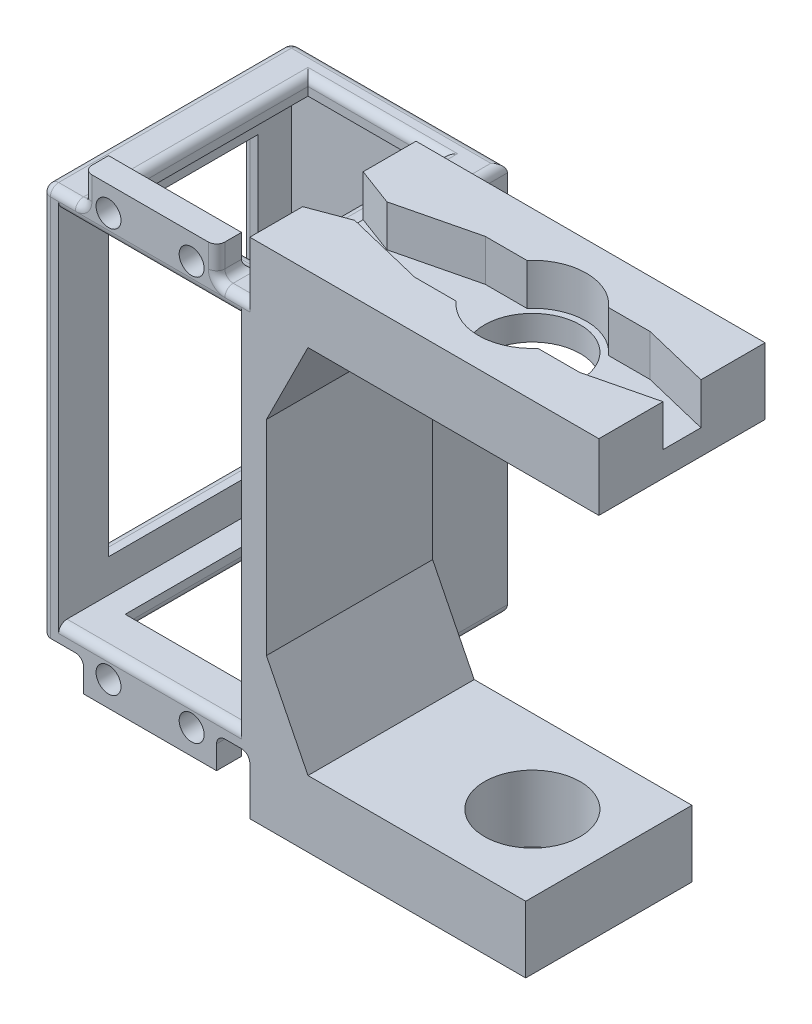
SolidWorks part; units mm, degrees
ref_plane "Front Plane" through (0, 0, 0) normal (0, 0, 1) x (1, 0, 0)
ref_plane "Top Plane" through (0, 0, 0) normal (0, 1, 0) x (1, 0, 0)
ref_plane "Right Plane" through (0, 0, 0) normal (1, 0, 0) x (0, 0, -1)
sketch "Sketch1" plane through (0, 0, 0) normal (0, 0, 1) x (1, 0, 0)
  line L1 (-13, 23.5) -> (13, 23.5)
  line L2 (-13, 23.5) -> (-13, -23.5)
  line L3 (-13, -23.5) -> (13, -23.5)
  line L4 (13, 23.5) -> (13, -23.5)
  line L5 (-13, 23.5) -> (13, -23.5) construction
  line L6 (-13, -23.5) -> (13, 23.5) construction
  point P0 (0, 0)
  dimension "D1" = 47
  dimension "D2" = 26
extrude "Boss-Extrude1" add sketch "Sketch1" along normal blind 30 contours L2 L1 L4 L3
shell "Shell1" thickness 2
sketch "Sketch2" plane through (0, 0, 30) normal (0, 0, 1) x (1, 0, 0)
  line L1 (-5, 24.3) -> (5, 24.3)
  line L2 (-5, 24.3) -> (-5, -24.3)
  line L3 (-5, -24.3) -> (5, -24.3)
  line L4 (5, 24.3) -> (5, -24.3)
  line L5 (-5, 24.3) -> (5, -24.3) construction
  line L6 (-5, -24.3) -> (5, 24.3) construction
  line L10 (-8, 27.3) -> (-8, -27.3)
  line L11 (-13, 23.5) -> (13, 23.5)
  line L12 (-13, 23.5) -> (-13, -23.5)
  line L13 (-13, -23.5) -> (13, -23.5)
  line L14 (13, 23.5) -> (13, -23.5)
  line L15 (-8, -27.3) -> (8, -27.3)
  line L16 (8, 27.3) -> (8, -27.3)
  line L17 (-8, 27.3) -> (8, 27.3)
  point P0 (0, 0)
  line M3 (-13, -23.5) -> (13, -23.5)
  line M5 (13, 23.5) -> (-13, 23.5)
  dimension "D1" = 10
  dimension "D2" = 48.6
  dimension "D3" = 3
extrude "Boss-Extrude2" add sketch "Sketch2" against normal blind 3 contours L17 L10 L2 L1 L4 L11 L16 M5 | L4 L1 L2 M5 | L16 L4 L3 L2 L10 L15 M3 | L4 L2 L3 M3
sketch "Sketch3" plane through (0, 0, 30) normal (0, 0, 1) x (1, 0, 0)
  line L1 (-5, 24.3) -> (5, 24.3) construction
  line L2 (-5, 24.3) -> (-5, -24.3) construction
  line L3 (-5, -24.3) -> (5, -24.3) construction
  line L4 (5, 24.3) -> (5, -24.3) construction
  line L5 (-5, 24.3) -> (5, -24.3) construction
  line L6 (-5, -24.3) -> (5, 24.3) construction
  circle A0 centre (-5, -24.3) radius 1.5
  circle A1 centre (5, -24.3) radius 1.5
  circle A2 centre (5, 24.3) radius 1.5
  circle A3 centre (-5, 24.3) radius 1.5
  point P0 (0, 0)
  dimension "D3" = 3
  dimension "D1" = 48.6
  dimension "D2" = 10
extrude "Cut-Extrude1" cut sketch "Sketch3" against normal blind 3
sketch "Sketch4" plane through (0, 0, 30) normal (0, 0, 1) x (1, 0, 0)
  line L0 (14, 0) -> (24, 0) construction
  line L1 (-24, 22.3) -> (24, 22.3)
  line L2 (-24, 22.3) -> (-24, -22.3)
  line L3 (-24, -22.3) -> (24, -22.3)
  line L4 (24, 22.3) -> (24, -22.3)
  line L5 (-24, 22.3) -> (24, -22.3) construction
  line L6 (-24, -22.3) -> (24, 22.3) construction
  line L7 (24, -22.3) -> (14, -22.3)
  line L8 (24, -22.3) -> (24, 22.3)
  line L9 (24, 22.3) -> (14, 22.3)
  line L10 (14, -22.3) -> (14, 22.3)
  line L11 (0, 0) -> (13, 0)
  line L12 (0, 0) -> (0, 23.5)
  line L13 (0, 23.5) -> (13, 23.5)
  line L14 (13, 0) -> (13, 23.5)
  line L15 (12, 22.3) -> (54, 22.3)
  line L16 (12, 22.3) -> (12, 30.3)
  line L17 (12, 30.3) -> (54, 30.3)
  line L18 (54, 22.3) -> (54, 30.3)
  line L19 (14, 12.3) -> (19, 22.3)
  line L20 (14, -12.3) -> (19, -22.3)
  line L21 (12, -30.3) -> (54, -30.3)
  line L22 (54, -22.3) -> (54, -30.3)
  line L23 (12, -22.3) -> (54, -22.3)
  line L24 (12, -22.3) -> (12, -30.3)
  point P0 (0, 0)
  point P8 (19, 22.3)
  point P20 (14, 12.3)
  line M10 (13, -23.5) -> (13, 23.5)
  dimension "D1" = 48
  dimension "D2" = 44.6
  dimension "D3" = 10
  dimension "D4" = 5
  dimension "D5" = 8
  dimension "D6" = 42
  dimension "D7" = 10
extrude "Boss-Extrude3" add sketch "Sketch4" against normal blind 20 contours L15 L18 L17 L16 L1 M10 | L10 L19 L1 | L3 L10 L1 M10 | L20 L10 L3 | L24 L21 L22 L23 L7 L3 M10
sketch "Sketch5" plane through (0, 22.3, 0) normal (0, -1, 0) x (-1, 0, 0)
  line L0 (-36, -30) -> (-36, -10)
  line L1 (-19, -10) -> (-54, -10)
  line L2 (-19, -10) -> (-19, -30)
  line L3 (-19, -30) -> (-54, -30)
  line L4 (-54, -10) -> (-54, -30)
  circle A0 centre (-36, -20) radius 5.75
  dimension "D2" = 11.5
  dimension "D1" = 17
extrude "Cut-Extrude2" cut sketch "Sketch5" against normal through all both and the other way through all contours L0 A0 | L0 A0
sketch "Sketch6" plane through (0, 0, 0) normal (0, 0, -1) x (-1, 0, 0)
  line L1 (-13, 23.5) -> (13, 23.5)
  line L2 (-13, 23.5) -> (-13, -23.5)
  line L3 (-13, -23.5) -> (13, -23.5)
  line L4 (13, 23.5) -> (13, -23.5)
  circle A0 centre (0, 0) radius 4.5
  circle A1 centre (0, -10) radius 4.5
  dimension "D1" = 9
  dimension "D2" = 2
extrude "Boss-Extrude4" add sketch "Sketch6" along normal blind 8 contours A1
sketch "Sketch7" plane through (0, 23.5, 0) normal (0, 1, 0) x (1, 0, 0)
  line L0 (8, -25) -> (8, -5)
  line L1 (13, -30) -> (-13, -30)
  line L2 (13, -30) -> (13, 0)
  line L3 (13, 0) -> (-13, 0)
  line L4 (-13, -30) -> (-13, 0)
  line L5 (8, -5) -> (-8, -5) construction
  line L6 (-8, -25) -> (-8, -5)
  line L7 (8, -25) -> (-8, -25)
  line L8 (8, -23) -> (8, -3)
  line L9 (8, -3) -> (-8, -3)
  line L10 (-8, -23) -> (-8, -3)
  line L11 (8, -23) -> (-8, -23) construction
  point P10 (13, 0)
  dimension "3" = 3
  dimension "D1" = 5
  dimension "D2" = 2
extrude "Cut-Extrude3" cut sketch "Sketch7" against normal through all both and the other way through all contours L10 L6 L7 L0 L8 L9
sketch "Sketch9" plane through (0, 30.3, 0) normal (0, 1, 0) x (1, 0, 0)
  line L0 (31.0819, -24.25) -> (31.0819, -15.75)
  line L1 (-30, 10) -> (54, 10)
  line L2 (-30, 10) -> (-30, -30)
  line L3 (-30, -30) -> (54, -30)
  line L4 (54, 10) -> (54, -30)
  line L5 (-30, 10) -> (54, -30) construction
  line L6 (-30, -30) -> (54, 10) construction
  line L7 (36, -20) -> (29.5, -20) construction
  line L8 (31.0819, -15.75) -> (26.0819, -15.75)
  line L9 (31.0819, -24.25) -> (26.0819, -24.25)
  line L10 (26.0819, -15.75) -> (16.5595, -18.066)
  line L11 (26.0819, -24.25) -> (16.5595, -21.934)
  line L12 (16.5595, -18.066) -> (10.3634, -15.75)
  line L13 (10.3634, -15.75) -> (10.3634, -22.7485)
  line L14 (10.3634, -22.7485) -> (10.3634, -24.25)
  line L15 (10.3634, -24.25) -> (16.5595, -21.934)
  line L16 (36, -20) -> (36, -13.5) construction
  line L17 (61.6366, -22.7485) -> (61.6366, -24.25)
  line L18 (61.6366, -15.75) -> (61.6366, -22.7485)
  line L19 (55.4405, -18.066) -> (61.6366, -15.75)
  line L20 (45.9181, -15.75) -> (55.4405, -18.066)
  line L21 (40.9181, -15.75) -> (45.9181, -15.75)
  line L22 (40.9181, -24.25) -> (40.9181, -15.75)
  line L23 (40.9181, -24.25) -> (45.9181, -24.25)
  line L24 (45.9181, -24.25) -> (55.4405, -21.934)
  line L25 (61.6366, -24.25) -> (55.4405, -21.934)
  circle A0 centre (36, -20) radius 6.5
  circle A1 centre (26.0819, -15.75) radius 9.8 construction
  point P0 (12, -10)
  dimension "D1" = 13
  dimension "D5" = 19.6
  dimension "D2" = 8.5
  dimension "D3" = 5
  dimension "D4" = 166.33
extrude "Cut-Extrude4" cut sketch "Sketch9" against normal blind 5
sketch "Sketch10" plane through (-13, 0, 0) normal (-1, 0, 0) x (0, 0, 1)
  line L0 (6, 17.5) -> (6, -17.5)
  line L1 (0, 23.5) -> (30, 23.5)
  line L2 (0, 23.5) -> (0, -23.5)
  line L3 (0, -23.5) -> (30, -23.5)
  line L4 (30, 23.5) -> (30, -23.5)
  line L5 (6, -17.5) -> (24, -17.5)
  line L6 (24, 17.5) -> (24, -17.5)
  line L7 (6, 17.5) -> (24, 17.5)
  dimension "D1" = 6
extrude "Cut-Extrude5" cut sketch "Sketch10" against normal blind 5 contours L0 L5 L6 L7
fillet "Fillet1" radius 1 5 edges at (0, -21.5, 30) (-13, 0, 6) (-13, -17.5, 15) (-13, 0, 24) (-13, 17.5, 15)
fillet "Fillet2" radius 1 3 edges at (8, 23.5, 28.5) (-8, 23.5, 28.5) (12, -23.5, 20)
fillet "Fillet3" radius 1 2 edges at (-8, -23.5, 28.5) (8, -23.5, 28.5)
fillet "Fillet5" radius 1 23 edges at (-11, 23.5, 30) (-8, 23.5, 14) (0, 23.5, 3) (0, -23.5, 3) (8, 23.5, 14) (8, -23.5, 14) (0, 23.5, 25) (-8, -23.5, 14) (0, -23.5, 25) (-13, 0, 30) (8, 25.9, 30) (10.5, 23.5, 30) (-8, 25.9, 30) (-8.2929, 23.7929, 30) (8.2929, 23.7929, 30) (-13, 0, 0) (0, 23.5, 0) (0, -23.5, 0) (-13, -23.5, 15) (-13, 23.5, 15) (13, 23.5, 5) (13, -23.5, 5) (12.5, 23.5, 10)
fillet "Fillet6" radius 1 1 edges at (0, 21.5, 30)
sketch "Sketch11" plane through (0, -30.3, 0) normal (0, -1, 0) x (1, 0, 0)
  line L0 (12, 10) -> (54, 10) construction
  line L1 (54, 30) -> (45.1981, 30)
  line L2 (54, 30) -> (54, 10)
  line L3 (54, 10) -> (45.1981, 10)
  line L4 (45.1981, 30) -> (45.1981, 10)
  dimension "D1" = 8.8019
extrude "Cut-Extrude6" cut sketch "Sketch11" against normal blind 10 contours L2 L1 L4 L3
